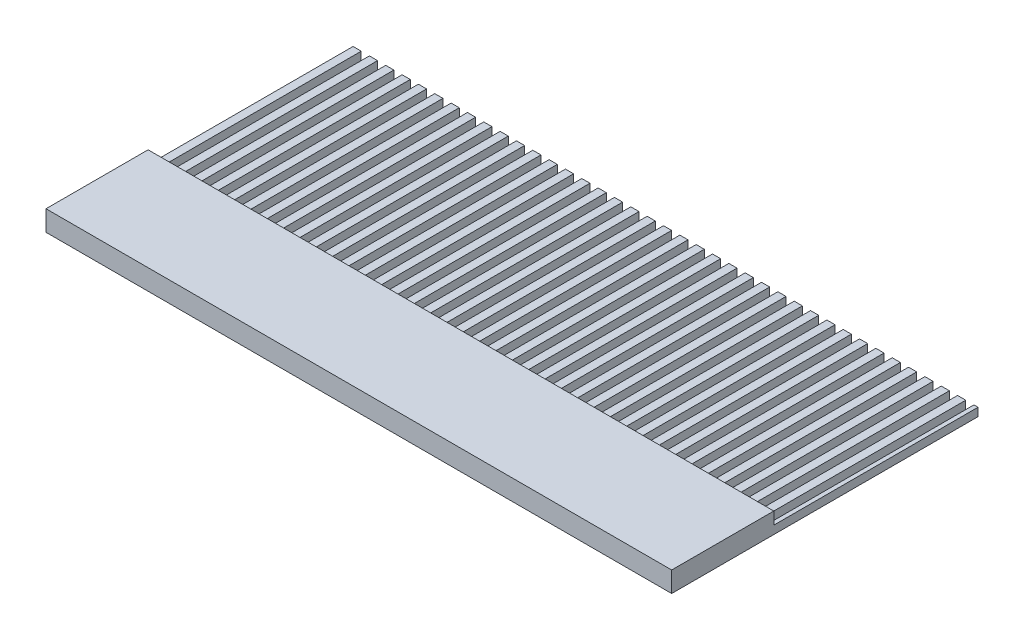
SolidWorks part; units mm, degrees
ref_plane "Front Plane" through (0, 0, 0) normal (0, 0, 1) x (1, 0, 0)
ref_plane "Top Plane" through (0, 0, 0) normal (0, 1, 0) x (1, 0, 0)
ref_plane "Right Plane" through (0, 0, 0) normal (1, 0, 0) x (0, 0, -1)
sketch "Sketch1" plane through (0, 0, 0) normal (0, 1, 0) x (1, 0, 0)
  line L1 (0, 0) -> (115, 0)
  line L2 (0, 0) -> (0, 15)
  line L3 (0, 15) -> (115, 15)
  line L4 (115, 0) -> (115, 15)
extrude "Boss-Extrude1" add sketch "Sketch1" along normal blind 0.5
sketch "Sketch2" plane through (0, 0.5, 0) normal (0, 1, 0) x (1, 0, 0)
  line L0 (115, 0) -> (115, 15) construction
  line L1 (0, 15) -> (115, 15)
  line L2 (0, 15) -> (0, 5)
  line L3 (0, 5) -> (115, 5)
  line L4 (115, 15) -> (115, 5)
extrude "Cut-Extrude1" cut sketch "Sketch2" against normal blind 0.1
sketch "Sketch3" plane through (0, 0.4, 0) normal (0, 1, 0) x (1, 0, 0)
  line L0 (0, 5) -> (115, 5) construction
  line L1 (0, 15) -> (0.4, 15)
  line L2 (0, 15) -> (0, 5)
  line L3 (0, 5) -> (0.4, 5)
  line L4 (0.4, 15) -> (0.4, 5)
extrude "Cut-Extrude2" cut sketch "Sketch3" against normal blind 0.4
pattern_linear "LPattern3" count 150 spacing 0.8 along (1, 0, 0) of "Cut-Extrude2"
sketch "Sketch4" plane through (0, 0, 0) normal (0, -1, 0) x (1, 0, 0)
  line L0 (0, -5) -> (0, 0) construction
  line L1 (0, -5) -> (115, -5)
  line L2 (0, -5) -> (0, 0)
  line L3 (0, 0) -> (115, 0)
  line L4 (115, -5) -> (115, 0)
  line L5 (0, -5) -> (0.4, -5) construction
extrude "Boss-Extrude2" add sketch "Sketch4" against normal blind 1
sketch "Sketch5" plane through (0, 1, 0) normal (0, 1, 0) x (1, 0, 0)
  line L1 (0, 0) -> (77.2891, 0)
  line L2 (0, 0) -> (0, 15.8221)
  line L3 (0, 15.8221) -> (77.2891, 15.8221)
  line L4 (77.2891, 0) -> (77.2891, 15.8221)
extrude "Cut-Extrude3" cut sketch "Sketch5" against normal blind 1
sketch "Sketch6" plane through (0, 1, 0) normal (0, 1, 0) x (1, 0, 0)
  line L1 (77.2891, 0) -> (80.4862, 0)
  line L2 (77.2891, 0) -> (77.2891, 15.0666)
  line L3 (77.2891, 15.0666) -> (80.4862, 15.0666)
  line L4 (80.4862, 0) -> (80.4862, 15.0666)
extrude "Cut-Extrude4" cut sketch "Sketch6" against normal blind 1
sketch "Sketch7" plane through (0, 1, 0) normal (0, 1, 0) x (1, 0, 0)
  line L1 (80.4862, 0) -> (84.3639, 0)
  line L2 (80.4862, 0) -> (80.4862, 15.1262)
  line L3 (80.4862, 15.1262) -> (84.3639, 15.1262)
  line L4 (84.3639, 0) -> (84.3639, 15.1262)
extrude "Cut-Extrude7" cut sketch "Sketch7" against normal blind 1
